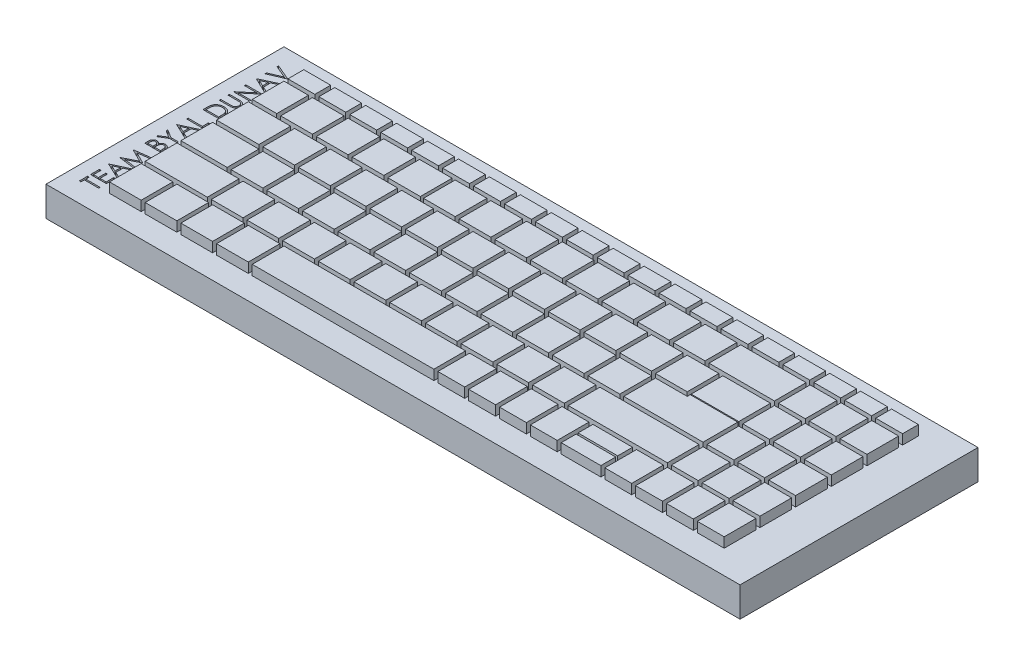
SolidWorks part; units mm, degrees
ref_plane "Front Plane" through (0, 0, 0) normal (0, 0, 1) x (1, 0, 0)
ref_plane "Top Plane" through (0, 0, 0) normal (0, 1, 0) x (1, 0, 0)
ref_plane "Right Plane" through (0, 0, 0) normal (1, 0, 0) x (0, 0, -1)
sketch "Sketch2" plane through (0, 0, 0) normal (0, 1, 0) x (1, 0, 0)
  line L0 (-175, 55) -> (-155, 55) construction
  line L1 (175, -60) -> (-175, -60)
  line L2 (175, -60) -> (175, 60)
  line L3 (175, 60) -> (-175, 60)
  line L4 (-175, -60) -> (-175, 60)
  line L5 (175, -60) -> (0, 0) construction
  line L6 (175, 60) -> (-175, -60) construction
  line L7 (-155, 60) -> (-155, 55) construction
  line L8 (155, 60) -> (155, -60) construction
  line L9 (0, 147.8519) -> (0, -167.8838) construction
  line L10 (-385.2931, 0) -> (301.8933, 0) construction
  line L11 (-175, -55) -> (175, -55) construction
  line L12 (-141.45, 55) -> (175, 55) construction
  line L19 (-160.4167, 55) -> (-175, 60) construction
  line L20 (-155, 47) -> (-155, -60) construction
  point P0 (0, 0)
  point P22 (-148.225, 51)
  dimension "D1" = 350
  dimension "D2" = 120
  dimension "D3" = 10
  dimension "D4" = 310
  dimension "D5" = 20
  dimension "D6" = 20
  dimension "D7" = 10
  dimension "D8" = 13.55
  dimension "D9" = 8
extrude "Boss-Extrude1" add sketch "Sketch2" along normal blind 15
sketch "Sketch3" plane through (0, 15, 0) normal (0, 1, 0) x (1, 0, 0)
  line L0 (-125.85, 50) -> (-125.85, 42)
  line L1 (155, -50) -> (-155, -50)
  line L2 (155, -50) -> (155, 50)
  line L3 (155, 50) -> (-155, 50)
  line L4 (-155, -50) -> (-155, 50)
  line L5 (175, -60) -> (175, 60) construction
  line L6 (-175, 60) -> (-175, -60) construction
  line L7 (-155, 50) -> (-141.45, 50)
  line L8 (-155, 50) -> (-155, 42)
  line L9 (-155, 42) -> (-141.45, 42)
  line L10 (-141.45, 50) -> (-141.45, 42)
  line L11 (175, 60) -> (-175, 60) construction
  line L12 (-141.45, 42) -> (-155, 42)
  line L13 (-141.45, 42) -> (-141.45, 50)
  line L14 (-141.45, 50) -> (-155, 50)
  line L15 (-155, 42) -> (-155, 50)
  line L16 (-141.45, 42) -> (-155, 50) construction
  line L17 (-141.45, 50) -> (-155, 42) construction
  line L18 (-141.45, 42) -> (-155, 42)
  line L19 (-141.45, 42) -> (-141.45, 50)
  line L20 (-141.45, 50) -> (-155, 50)
  line L21 (-155, 42) -> (-155, 50)
  line L22 (-141.45, 42) -> (-155, 50) construction
  line L23 (-141.45, 50) -> (-155, 42) construction
  line L24 (-139.4, 42) -> (-125.85, 42)
  line L25 (-110.25, 50) -> (-110.25, 42)
  line L26 (-123.8, 42) -> (-110.25, 42)
  line L27 (-94.65, 50) -> (-94.65, 42)
  line L28 (-108.2, 42) -> (-94.65, 42)
  line L29 (-79.05, 50) -> (-79.05, 42)
  line L30 (-92.6, 42) -> (-79.05, 42)
  line L31 (-63.45, 50) -> (-63.45, 42)
  line L32 (-77, 42) -> (-63.45, 42)
  line L33 (-47.85, 50) -> (-47.85, 42)
  line L34 (-61.4, 42) -> (-47.85, 42)
  line L35 (-32.25, 50) -> (-32.25, 42)
  line L36 (-45.8, 42) -> (-32.25, 42)
  line L37 (-16.65, 50) -> (-16.65, 42)
  line L38 (-30.2, 42) -> (-16.65, 42)
  line L39 (-1.05, 50) -> (-1.05, 42)
  line L40 (-14.6, 42) -> (-1.05, 42)
  line L41 (14.55, 50) -> (14.55, 42)
  line L42 (1, 42) -> (14.55, 42)
  line L43 (30.15, 50) -> (30.15, 42)
  line L44 (16.6, 42) -> (30.15, 42)
  line L45 (45.75, 50) -> (45.75, 42)
  line L46 (32.2, 42) -> (45.75, 42)
  line L47 (61.35, 50) -> (61.35, 42)
  line L48 (47.8, 42) -> (61.35, 42)
  line L49 (76.95, 50) -> (76.95, 42)
  line L50 (63.4, 42) -> (76.95, 42)
  line L51 (92.55, 50) -> (92.55, 42)
  line L52 (79, 42) -> (92.55, 42)
  line L53 (108.15, 50) -> (108.15, 42)
  line L54 (94.6, 42) -> (108.15, 42)
  line L55 (123.75, 50) -> (123.75, 42)
  line L56 (110.2, 42) -> (123.75, 42)
  line L57 (139.35, 50) -> (139.35, 42)
  line L58 (125.8, 42) -> (139.35, 42)
  line L59 (154.95, 50) -> (154.95, 42)
  line L60 (141.4, 42) -> (154.95, 42)
  line L61 (155, 40) -> (-155, 40) construction
  line L62 (-125.85, 42) -> (-139.4, 42)
  line L63 (-125.85, 42) -> (-125.85, 50)
  line L64 (-125.85, 50) -> (-139.4, 50)
  line L65 (-139.4, 42) -> (-139.4, 50)
  line L66 (-125.85, 42) -> (-139.4, 50) construction
  line L67 (-125.85, 50) -> (-139.4, 42) construction
  line L68 (-110.25, 42) -> (-123.8, 42)
  line L69 (-110.25, 42) -> (-110.25, 50)
  line L70 (-110.25, 50) -> (-123.8, 50)
  line L71 (-123.8, 42) -> (-123.8, 50)
  line L72 (-110.25, 42) -> (-123.8, 50) construction
  line L73 (-110.25, 50) -> (-123.8, 42) construction
  line L74 (-94.65, 42) -> (-108.2, 42)
  line L75 (-94.65, 42) -> (-94.65, 50)
  line L76 (-94.65, 50) -> (-108.2, 50)
  line L77 (-108.2, 42) -> (-108.2, 50)
  line L78 (-94.65, 42) -> (-108.2, 50) construction
  line L79 (-94.65, 50) -> (-108.2, 42) construction
  line L80 (-79.05, 42) -> (-92.6, 42)
  line L81 (-79.05, 42) -> (-79.05, 50)
  line L82 (-79.05, 50) -> (-92.6, 50)
  line L83 (-92.6, 42) -> (-92.6, 50)
  line L84 (-79.05, 42) -> (-92.6, 50) construction
  line L85 (-79.05, 50) -> (-92.6, 42) construction
  line L86 (-63.45, 42) -> (-77, 42)
  line L87 (-63.45, 42) -> (-63.45, 50)
  line L88 (-63.45, 50) -> (-77, 50)
  line L89 (-77, 42) -> (-77, 50)
  line L90 (-63.45, 42) -> (-77, 50) construction
  line L91 (-63.45, 50) -> (-77, 42) construction
  line L92 (-47.85, 42) -> (-61.4, 42)
  line L93 (-47.85, 42) -> (-47.85, 50)
  line L94 (-47.85, 50) -> (-61.4, 50)
  line L95 (-61.4, 42) -> (-61.4, 50)
  line L96 (-47.85, 42) -> (-61.4, 50) construction
  line L97 (-47.85, 50) -> (-61.4, 42) construction
  line L98 (-32.25, 42) -> (-45.8, 42)
  line L99 (-32.25, 42) -> (-32.25, 50)
  line L100 (-32.25, 50) -> (-45.8, 50)
  line L101 (-45.8, 42) -> (-45.8, 50)
  line L102 (-32.25, 42) -> (-45.8, 50) construction
  line L103 (-32.25, 50) -> (-45.8, 42) construction
  line L104 (-16.65, 42) -> (-30.2, 42)
  line L105 (-16.65, 42) -> (-16.65, 50)
  line L106 (-16.65, 50) -> (-30.2, 50)
  line L107 (-30.2, 42) -> (-30.2, 50)
  line L108 (-16.65, 42) -> (-30.2, 50) construction
  line L109 (-16.65, 50) -> (-30.2, 42) construction
  line L110 (-1.05, 42) -> (-14.6, 42)
  line L111 (-1.05, 42) -> (-1.05, 50)
  line L112 (-1.05, 50) -> (-14.6, 50)
  line L113 (-14.6, 42) -> (-14.6, 50)
  line L114 (-1.05, 42) -> (-14.6, 50) construction
  line L115 (-1.05, 50) -> (-14.6, 42) construction
  line L116 (14.55, 42) -> (1, 42)
  line L117 (14.55, 42) -> (14.55, 50)
  line L118 (14.55, 50) -> (1, 50)
  line L119 (1, 42) -> (1, 50)
  line L120 (14.55, 42) -> (1, 50) construction
  line L121 (14.55, 50) -> (1, 42) construction
  line L122 (30.15, 42) -> (16.6, 42)
  line L123 (30.15, 42) -> (30.15, 50)
  line L124 (30.15, 50) -> (16.6, 50)
  line L125 (16.6, 42) -> (16.6, 50)
  line L126 (30.15, 42) -> (16.6, 50) construction
  line L127 (30.15, 50) -> (16.6, 42) construction
  line L128 (45.75, 42) -> (32.2, 42)
  line L129 (45.75, 42) -> (45.75, 50)
  line L130 (45.75, 50) -> (32.2, 50)
  line L131 (32.2, 42) -> (32.2, 50)
  line L132 (45.75, 42) -> (32.2, 50) construction
  line L133 (45.75, 50) -> (32.2, 42) construction
  line L134 (61.35, 42) -> (47.8, 42)
  line L135 (61.35, 42) -> (61.35, 50)
  line L136 (61.35, 50) -> (47.8, 50)
  line L137 (47.8, 42) -> (47.8, 50)
  line L138 (61.35, 42) -> (47.8, 50) construction
  line L139 (61.35, 50) -> (47.8, 42) construction
  line L140 (76.95, 42) -> (63.4, 42)
  line L141 (76.95, 42) -> (76.95, 50)
  line L142 (76.95, 50) -> (63.4, 50)
  line L143 (63.4, 42) -> (63.4, 50)
  line L144 (76.95, 42) -> (63.4, 50) construction
  line L145 (76.95, 50) -> (63.4, 42) construction
  line L146 (92.55, 42) -> (79, 42)
  line L147 (92.55, 42) -> (92.55, 50)
  line L148 (92.55, 50) -> (79, 50)
  line L149 (79, 42) -> (79, 50)
  line L150 (92.55, 42) -> (79, 50) construction
  line L151 (92.55, 50) -> (79, 42) construction
  line L152 (108.15, 42) -> (94.6, 42)
  line L153 (108.15, 42) -> (108.15, 50)
  line L154 (108.15, 50) -> (94.6, 50)
  line L155 (94.6, 42) -> (94.6, 50)
  line L156 (108.15, 42) -> (94.6, 50) construction
  line L157 (108.15, 50) -> (94.6, 42) construction
  line L158 (123.75, 42) -> (110.2, 42)
  line L159 (123.75, 42) -> (123.75, 50)
  line L160 (123.75, 50) -> (110.2, 50)
  line L161 (110.2, 42) -> (110.2, 50)
  line L162 (123.75, 42) -> (110.2, 50) construction
  line L163 (123.75, 50) -> (110.2, 42) construction
  line L164 (139.35, 42) -> (125.8, 42)
  line L165 (139.35, 42) -> (139.35, 50)
  line L166 (139.35, 50) -> (125.8, 50)
  line L167 (125.8, 42) -> (125.8, 50)
  line L168 (139.35, 42) -> (125.8, 50) construction
  line L169 (139.35, 50) -> (125.8, 42) construction
  line L170 (154.95, 42) -> (141.4, 42)
  line L171 (154.95, 42) -> (154.95, 50)
  line L172 (154.95, 50) -> (141.4, 50)
  line L173 (141.4, 42) -> (141.4, 50)
  line L174 (154.95, 42) -> (141.4, 50) construction
  line L175 (154.95, 50) -> (141.4, 42) construction
  line L176 (55.35, 24) -> (39.35, 24)
  line L177 (155, 40) -> (141.45, 40)
  line L178 (155, 40) -> (155, 24)
  line L179 (155, 24) -> (141.45, 24)
  line L180 (141.45, 40) -> (141.45, 24)
  line L181 (155, 40) -> (141.45, 24) construction
  line L182 (155, 24) -> (141.45, 40) construction
  line L183 (139.45, 40) -> (125.9, 40)
  line L184 (139.45, 40) -> (139.45, 24)
  line L185 (139.45, 24) -> (125.9, 24)
  line L186 (125.9, 40) -> (125.9, 24)
  line L187 (139.45, 40) -> (125.9, 24) construction
  line L188 (139.45, 24) -> (125.9, 40) construction
  line L189 (123.9, 40) -> (110.35, 40)
  line L191 (123.9, 24) -> (110.35, 24)
  line L192 (110.35, 40) -> (110.35, 24)
  line L193 (123.9, 40) -> (110.35, 24) construction
  line L194 (123.9, 24) -> (110.35, 40) construction
  line L195 (108.35, 40) -> (75.35, 40)
  line L196 (108.35, 40) -> (108.35, 24)
  line L197 (108.35, 24) -> (75.35, 24)
  line L198 (75.35, 40) -> (75.35, 24)
  line L199 (108.35, 40) -> (75.35, 24) construction
  line L200 (108.35, 24) -> (75.35, 40) construction
  line L201 (73.35, 40) -> (57.35, 40)
  line L202 (73.35, 40) -> (73.35, 24)
  line L203 (73.35, 24) -> (57.35, 24)
  line L204 (57.35, 40) -> (57.35, 24)
  line L205 (73.35, 40) -> (57.35, 24) construction
  line L206 (73.35, 24) -> (57.35, 40) construction
  line L207 (39.35, 40) -> (39.35, 24)
  line L208 (37.35, 24) -> (21.35, 24)
  line L209 (21.35, 40) -> (21.35, 24)
  line L210 (19.35, 24) -> (3.35, 24)
  line L211 (3.35, 40) -> (3.35, 24)
  line L212 (1.35, 24) -> (-14.65, 24)
  line L213 (-14.65, 40) -> (-14.65, 24)
  line L214 (-16.65, 24) -> (-32.65, 24)
  line L215 (-32.65, 40) -> (-32.65, 24)
  line L216 (-34.65, 24) -> (-50.65, 24)
  line L217 (-50.65, 40) -> (-50.65, 24)
  line L218 (-52.65, 24) -> (-68.65, 24)
  line L219 (-68.65, 40) -> (-68.65, 24)
  line L220 (-70.65, 24) -> (-86.65, 24)
  line L221 (-86.65, 40) -> (-86.65, 24)
  line L222 (-88.65, 24) -> (-104.65, 24)
  line L223 (-104.65, 40) -> (-104.65, 24)
  line L224 (-106.65, 24) -> (-122.65, 24)
  line L225 (-122.65, 40) -> (-122.65, 24)
  line L226 (-124.65, 24) -> (-140.65, 24)
  line L227 (-140.65, 40) -> (-140.65, 24)
  line L228 (55.35, 24) -> (55.35, 40)
  line L229 (55.35, 40) -> (39.35, 40)
  line L230 (123.9, 40) -> (123.9, 24)
  line L231 (21.35, 24) -> (37.35, 24)
  line L232 (21.35, 24) -> (21.35, 40)
  line L233 (21.35, 40) -> (37.35, 40)
  line L234 (37.35, 24) -> (37.35, 40)
  line L235 (21.35, 24) -> (37.35, 40) construction
  line L236 (21.35, 40) -> (37.35, 24) construction
  line L237 (3.35, 24) -> (19.35, 24)
  line L238 (3.35, 24) -> (3.35, 40)
  line L239 (3.35, 40) -> (19.35, 40)
  line L240 (19.35, 24) -> (19.35, 40)
  line L241 (3.35, 24) -> (19.35, 40) construction
  line L242 (3.35, 40) -> (19.35, 24) construction
  line L243 (-14.65, 24) -> (1.35, 24)
  line L244 (-14.65, 24) -> (-14.65, 40)
  line L245 (-14.65, 40) -> (1.35, 40)
  line L246 (1.35, 24) -> (1.35, 40)
  line L247 (-14.65, 24) -> (1.35, 40) construction
  line L248 (-14.65, 40) -> (1.35, 24) construction
  line L249 (-32.65, 24) -> (-16.65, 24)
  line L250 (-32.65, 24) -> (-32.65, 40)
  line L251 (-32.65, 40) -> (-16.65, 40)
  line L252 (-16.65, 24) -> (-16.65, 40)
  line L253 (-32.65, 24) -> (-16.65, 40) construction
  line L254 (-32.65, 40) -> (-16.65, 24) construction
  line L255 (-50.65, 24) -> (-34.65, 24)
  line L256 (-50.65, 24) -> (-50.65, 40)
  line L257 (-50.65, 40) -> (-34.65, 40)
  line L258 (-34.65, 24) -> (-34.65, 40)
  line L259 (-50.65, 24) -> (-34.65, 40) construction
  line L260 (-50.65, 40) -> (-34.65, 24) construction
  line L261 (-68.65, 24) -> (-52.65, 24)
  line L262 (-68.65, 24) -> (-68.65, 40)
  line L263 (-68.65, 40) -> (-52.65, 40)
  line L264 (-52.65, 24) -> (-52.65, 40)
  line L265 (-68.65, 24) -> (-52.65, 40) construction
  line L266 (-68.65, 40) -> (-52.65, 24) construction
  line L267 (-86.65, 24) -> (-70.225, 24)
  line L268 (-86.65, 24) -> (-86.65, 40)
  line L269 (-86.65, 40) -> (-70.225, 40)
  line L270 (-70.225, 24) -> (-70.225, 40)
  line L271 (-86.65, 24) -> (-70.225, 40) construction
  line L272 (-86.65, 40) -> (-70.225, 24) construction
  line L273 (-104.65, 24) -> (-88.65, 24)
  line L274 (-104.65, 24) -> (-104.65, 40)
  line L275 (-104.65, 40) -> (-88.65, 40)
  line L276 (-88.65, 24) -> (-88.65, 40)
  line L277 (-104.65, 24) -> (-88.65, 40) construction
  line L278 (-104.65, 40) -> (-88.65, 24) construction
  line L279 (-122.65, 24) -> (-106.65, 24)
  line L280 (-122.65, 24) -> (-122.65, 40)
  line L281 (-122.65, 40) -> (-106.65, 40)
  line L282 (-106.65, 24) -> (-106.65, 40)
  line L283 (-122.65, 24) -> (-106.65, 40) construction
  line L284 (-122.65, 40) -> (-106.65, 24) construction
  line L285 (-140.65, 24) -> (-124.65, 24)
  line L286 (-140.65, 24) -> (-140.65, 40)
  line L287 (-140.65, 40) -> (-124.65, 40)
  line L288 (-124.65, 24) -> (-124.65, 40)
  line L289 (-140.65, 24) -> (-124.65, 40) construction
  line L290 (-140.65, 40) -> (-124.65, 24) construction
  line L291 (-155, 40) -> (-142.65, 40)
  line L292 (-155, 40) -> (-155, 24)
  line L293 (-155, 24) -> (-142.65, 24)
  line L294 (-142.65, 40) -> (-142.65, 24)
  line L295 (-155, 40) -> (-142.65, 24) construction
  line L296 (-155, 24) -> (-142.65, 40) construction
  line L297 (110.35, 22) -> (110.35, 6)
  line L298 (123.9, 22) -> (123.9, 6)
  line L299 (123.9, 6) -> (110.35, 6)
  line L300 (125.9, 22) -> (125.9, 6)
  line L301 (139.45, 6) -> (125.9, 6)
  line L302 (139.45, 22) -> (139.45, 6)
  line L303 (141.45, 22) -> (141.45, 6)
  line L304 (155, 6) -> (141.45, 6)
  line L305 (110.35, 4) -> (110.35, -12)
  line L306 (123.9, 4) -> (123.9, -12)
  line L307 (123.9, -12) -> (110.35, -12)
  line L308 (125.9, 4) -> (125.9, -12)
  line L309 (139.45, -12) -> (125.9, -12)
  line L310 (139.45, 4) -> (139.45, -12)
  line L311 (141.45, 4) -> (141.45, -12)
  line L312 (155, -12) -> (141.45, -12)
  line L313 (110.35, -14) -> (110.35, -30)
  line L314 (123.9, -14) -> (123.9, -30)
  line L315 (123.9, -30) -> (110.35, -30)
  line L316 (125.9, -14) -> (125.9, -30)
  line L317 (139.45, -30) -> (125.9, -30)
  line L318 (139.45, -14) -> (139.45, -30)
  line L319 (141.45, -14) -> (141.45, -30)
  line L320 (155, -30) -> (141.45, -30)
  line L321 (110.35, -32) -> (110.35, -48)
  line L322 (123.9, -32) -> (123.9, -48)
  line L323 (123.9, -48) -> (110.35, -48)
  line L324 (125.9, -32) -> (125.9, -48)
  line L325 (139.45, -48) -> (125.9, -48)
  line L326 (139.45, -32) -> (139.45, -48)
  line L327 (141.45, -32) -> (141.45, -48)
  line L328 (155, -48) -> (141.45, -48)
  line L329 (110.35, 22) -> (123.9, 22)
  line L330 (125.9, 22) -> (139.45, 22)
  line L331 (141.45, 22) -> (155, 22)
  line L332 (110.35, 4) -> (123.9, 4)
  line L333 (125.9, 4) -> (139.45, 4)
  line L334 (141.45, 4) -> (155, 4)
  line L335 (110.35, -14) -> (123.9, -14)
  line L336 (125.9, -14) -> (139.45, -14)
  line L337 (141.45, -14) -> (155, -14)
  line L338 (110.35, -32) -> (123.9, -32)
  line L339 (125.9, -32) -> (139.45, -32)
  line L340 (141.45, -32) -> (155, -32)
  line L341 (155, 22) -> (-155, 22) construction
  line L342 (155, 6) -> (-155, 6) construction
  line L343 (48.35, 22) -> (48.35, 6)
  line L344 (108.35, 22) -> (84.35, 22)
  line L345 (108.35, 22) -> (108.35, 6)
  line L346 (108.35, 6) -> (84.35, 6)
  line L347 (84.35, 22) -> (84.35, 6)
  line L348 (108.35, 22) -> (84.35, 6) construction
  line L349 (108.35, 6) -> (84.35, 22) construction
  line L350 (82.35, 22) -> (66.35, 22)
  line L351 (82.35, 22) -> (82.35, 6)
  line L352 (82.35, 6) -> (66.35, 6)
  line L353 (66.35, 22) -> (66.35, 6)
  line L354 (82.35, 22) -> (66.35, 6) construction
  line L355 (82.35, 6) -> (66.35, 22) construction
  line L356 (64.35, 6) -> (48.35, 6)
  line L357 (30.35, 22) -> (30.35, 6)
  line L358 (46.35, 6) -> (30.35, 6)
  line L359 (12.35, 22) -> (12.35, 6)
  line L360 (28.35, 6) -> (12.35, 6)
  line L361 (-5.65, 22) -> (-5.65, 6)
  line L362 (10.35, 6) -> (-5.65, 6)
  line L363 (-23.65, 22) -> (-23.65, 6)
  line L364 (-7.65, 6) -> (-23.65, 6)
  line L365 (-41.65, 22) -> (-41.65, 6)
  line L366 (-25.65, 6) -> (-41.65, 6)
  line L367 (-59.65, 22) -> (-59.65, 6)
  line L368 (-43.65, 6) -> (-59.65, 6)
  line L369 (-77.65, 22) -> (-77.65, 6)
  line L370 (-61.65, 6) -> (-77.65, 6)
  line L371 (-95.65, 22) -> (-95.65, 6)
  line L372 (-79.65, 6) -> (-95.65, 6)
  line L373 (-113.65, 22) -> (-113.65, 6)
  line L374 (-97.65, 6) -> (-113.65, 6)
  line L375 (-131.65, 22) -> (-131.65, 6)
  line L376 (-115.65, 6) -> (-131.65, 6)
  line L377 (28.35, 6) -> (28.35, 22)
  line L378 (-131.65, 6) -> (-115.65, 6)
  line L379 (-131.65, 6) -> (-131.65, 22)
  line L380 (-131.65, 22) -> (-115.65, 22)
  line L381 (-115.65, 6) -> (-115.65, 22)
  line L382 (-131.65, 6) -> (-115.65, 22) construction
  line L383 (-131.65, 22) -> (-115.65, 6) construction
  line L384 (-113.65, 6) -> (-97.65, 6)
  line L385 (-113.65, 6) -> (-113.65, 22)
  line L386 (-113.65, 22) -> (-97.65, 22)
  line L387 (-97.65, 6) -> (-97.65, 22)
  line L388 (-113.65, 6) -> (-97.65, 22) construction
  line L389 (-113.65, 22) -> (-97.65, 6) construction
  line L390 (-95.65, 6) -> (-79.65, 6)
  line L391 (-95.65, 6) -> (-95.65, 22)
  line L392 (-95.65, 22) -> (-79.65, 22)
  line L393 (-79.65, 6) -> (-79.65, 22)
  line L394 (-95.65, 6) -> (-79.65, 22) construction
  line L395 (-95.65, 22) -> (-79.65, 6) construction
  line L396 (-77.65, 6) -> (-61.65, 6)
  line L397 (-77.65, 6) -> (-77.65, 22)
  line L398 (-77.65, 22) -> (-61.65, 22)
  line L399 (-61.65, 6) -> (-61.65, 22)
  line L400 (-77.65, 6) -> (-61.65, 22) construction
  line L401 (-77.65, 22) -> (-61.65, 6) construction
  line L402 (-59.65, 6) -> (-43.65, 6)
  line L403 (-59.65, 6) -> (-59.65, 22)
  line L404 (-59.65, 22) -> (-43.65, 22)
  line L405 (-43.65, 6) -> (-43.65, 22)
  line L406 (-59.65, 6) -> (-43.65, 22) construction
  line L407 (-59.65, 22) -> (-43.65, 6) construction
  line L408 (-41.65, 6) -> (-25.65, 6)
  line L409 (-41.65, 6) -> (-41.65, 22)
  line L410 (-41.65, 22) -> (-25.65, 22)
  line L411 (-25.65, 6) -> (-25.65, 22)
  line L412 (-41.65, 6) -> (-25.65, 22) construction
  line L413 (-41.65, 22) -> (-25.65, 6) construction
  line L414 (-23.65, 6) -> (-7.65, 6)
  line L415 (-23.65, 6) -> (-23.65, 22)
  line L416 (-23.65, 22) -> (-7.65, 22)
  line L417 (-7.65, 6) -> (-7.65, 22)
  line L418 (-23.65, 6) -> (-7.65, 22) construction
  line L419 (-23.65, 22) -> (-7.65, 6) construction
  line L420 (10.35, 6) -> (-5.65, 6)
  line L421 (10.35, 6) -> (10.35, 22)
  line L422 (10.35, 22) -> (-5.65, 22)
  line L423 (-5.65, 6) -> (-5.65, 22)
  line L424 (10.35, 6) -> (-5.65, 22) construction
  line L425 (10.35, 22) -> (-5.65, 6) construction
  line L426 (28.35, 22) -> (12.35, 22)
  line L427 (46.35, 6) -> (46.35, 22)
  line L428 (46.35, 22) -> (30.35, 22)
  line L429 (64.35, 6) -> (64.35, 22)
  line L430 (64.35, 22) -> (48.35, 22)
  line L432 (-155, 6) -> (-133.65, 6)
  line L433 (-155, 6) -> (-155, 22)
  line L434 (-155, 22) -> (-133.65, 22)
  line L435 (-133.65, 6) -> (-133.65, 22)
  line L436 (-155, 6) -> (-133.65, 22) construction
  line L437 (-155, 22) -> (-133.65, 6) construction
  point P0 (0, 0)
  point P9 (-148.225, 47.8145)
  point P17 (-148.225, 46)
  point P18 (-148.225, 46)
  point P20 (-132.625, 46)
  point P78 (-117.025, 46)
  point P80 (-101.425, 46)
  point P82 (-85.825, 46)
  point P84 (-70.225, 46)
  point P86 (-54.625, 46)
  point P88 (-39.025, 46)
  point P90 (-23.425, 46)
  point P92 (-7.825, 46)
  point P94 (7.775, 46)
  point P96 (23.375, 46)
  point P98 (38.975, 46)
  point P100 (54.575, 46)
  point P102 (70.175, 46)
  point P104 (85.775, 46)
  point P106 (101.375, 46)
  point P108 (116.975, 46)
  point P110 (132.575, 46)
  point P112 (148.175, 46)
  point P118 (148.225, 32)
  point P123 (132.675, 32)
  point P128 (117.125, 32)
  point P133 (91.85, 32)
  point P134 (125.9, 32)
  point P139 (65.35, 32)
  point P175 (29.35, 32)
  point P177 (11.35, 32)
  point P179 (-6.65, 32)
  point P181 (-24.65, 32)
  point P183 (-42.65, 32)
  point P185 (-60.65, 32)
  point P188 (-78.4375, 32)
  point P190 (-96.65, 32)
  point P192 (-114.65, 32)
  point P194 (-132.65, 32)
  point P198 (-148.825, 32)
  point P199 (-142.65, 32)
  point P200 (21.35, 32)
  point P250 (117.125, 22)
  point P256 (96.35, 14)
  point P261 (74.35, 14)
  point P262 (82.35, 14)
  point P264 (-123.65, 14)
  point P299 (-105.65, 14)
  point P301 (-87.65, 14)
  point P303 (-69.65, 14)
  point P305 (-51.65, 14)
  point P307 (-33.65, 14)
  point P309 (-15.65, 14)
  point P312 (2.35, 14)
  point P318 (-144.325, 14)
  dimension "D1" = 310
  dimension "D2" = 100
  dimension "D3" = 13.55
  dimension "D4" = 8
  dimension "D5" = 20
  dimension "D6" = 20
  dimension "D7" = 10
  dimension "D8" = 20
  dimension "D9" = 2
  dimension "D10" = 16
  dimension "D11" = 13.55
  dimension "D12" = 2
  dimension "D13" = 13.55
  dimension "D14" = 16
  dimension "D15" = 16
  dimension "D16" = 16
  dimension "D17" = 16
  dimension "D18" = 33
  dimension "D19" = 2
  dimension "D20" = 5
  dimension "D21" = 2
  dimension "D22" = 16
  dimension "D23" = 12
  dimension "D24" = 2
  dimension "D25" = 2
  dimension "D26" = 2
  dimension "D27" = 2
  dimension "D28" = 12.35
  dimension "D29" = 2
  dimension "D30" = 16
  dimension "D31" = 2
  dimension "D32" = 24
  dimension "D33" = 2
  dimension "D34" = 16
  dimension "D35" = 2
  dimension "D36" = 12
  dimension "D37" = 2
  dimension "D38" = 2
extrude "Boss-Extrude2" add sketch "Sketch3" along normal blind 5 contours L10 L3 L4 L9 | L432 L435 L434 L4 | L226 L288 L287 L227 | L294 L291 L4 L293 | L65 L24 L0 L3 | L376 L381 L380 L375 | L374 L387 L386 L373 | L83 L30 L29 L3 | L267 L270 L269 L221 L220 | L372 L393 L392 L371 | L370 L399 L398 L369 | L222 L276 L275 L223 | L224 L282 L281 L225 | L71 L26 L25 L3 | L77 L28 L27 L3 | L89 L32 L31 L3 | L218 L264 L263 L219 | L95 L34 L33 L3 | L368 L405 L404 L367 | L216 L258 L257 L217 | L101 L36 L35 L3 | L214 L252 L251 L215 | L366 L411 L410 L365 | L364 L417 L416 L363 | L212 L246 L245 L213 | L107 L38 L37 L3 | L113 L40 L39 L3 | L119 L42 L41 L3 | L210 L240 L239 L211 | L421 L422 L361 L362 | L377 L426 L359 L360 | L125 L44 L43 L3 | L228 L229 L207 L176 | L208 L234 L233 L209 | L131 L46 L45 L3 | L427 L428 L357 L358 | L429 L430 L343 L356 | L201 L204 L203 L202 | L143 L50 L49 L3 | L137 L48 L47 L3 | L149 L52 L51 L3 | L350 L353 L352 L351 | L195 L198 L197 L196 | L344 L347 L346 L345 | L329 L297 L299 L298 | L230 L189 L192 L191 | L183 L186 L185 L184 | L331 L303 L304 L2 | L330 L300 L301 L302 | L332 L305 L307 L306 | L333 L308 L309 L310 | L334 L311 L312 L2 | L337 L319 L320 L2 | L335 L313 L315 L314 | L338 L321 L323 L322 | L340 L327 L328 L2 | L336 L316 L317 L318 | L339 L324 L325 L326 | L155 L54 L53 L3 | L173 L60 L59 L3 | L177 L180 L179 L2 | L161 L56 L55 L3 | L167 L58 L57 L3 region at (-132.625, 15, -46) region at (-117.025, 15, -46) region at (-148.225, 15, -46) region at (-101.425, 15, -46) region at (-85.825, 15, -46) region at (-148.825, 15, -32) region at (-70.225, 15, -46) region at (-144.325, 15, -14) region at (-54.625, 15, -46) region at (-39.025, 15, -46) region at (148.225, 15, 40) region at (-23.425, 15, -46) region at (148.225, 15, 22) region at (-7.825, 15, -46) region at (148.225, 15, 4) region at (7.775, 15, -46) region at (148.225, 15, -14) region at (23.375, 15, -46) region at (148.225, 15, -32) region at (38.975, 15, -46) region at (148.175, 15, -46) region at (54.575, 15, -46) region at (132.575, 15, -46) region at (70.175, 15, -46) region at (116.975, 15, -46) region at (85.775, 15, -46) region at (101.375, 15, -46) region at (47.35, 15, -32) region at (132.675, 15, -32) region at (117.125, 15, -32) region at (91.85, 15, -32) region at (65.35, 15, -32) region at (29.35, 15, -32) region at (11.35, 15, -32) region at (-6.65, 15, -32) region at (-24.65, 15, -32) region at (-42.65, 15, -32) region at (-60.65, 15, -32) region at (-78.4375, 15, -32) region at (-96.65, 15, -32) region at (-114.65, 15, -32) region at (-132.65, 15, -32) region at (117.125, 15, -14) region at (132.675, 15, -14) region at (117.125, 15, 4) region at (132.675, 15, 4) region at (117.125, 15, 22) region at (132.675, 15, 22) region at (117.125, 15, 40) region at (132.675, 15, 40) region at (56.35, 15, -14) region at (96.35, 15, -14) region at (74.35, 15, -14) region at (38.35, 15, -14) region at (20.35, 15, -14) region at (2.35, 15, -14) region at (-15.65, 15, -14) region at (-33.65, 15, -14) region at (-51.65, 15, -14) region at (-69.65, 15, -14)
sketch "Sketch4" plane through (0, 15, 0) normal (0, 1, 0) x (1, 0, 0)
  line L0 (155, -12) -> (-175, -12) construction
  line L1 (-175, 60) -> (-175, -60) construction
  line L2 (155, 4) -> (108.35, 4) construction
  line L3 (110.35, 4) -> (110.35, -12) construction
  line L4 (84.35, 4) -> (68.35, 4)
  line L5 (108.35, 4) -> (108.35, -12)
  line L6 (108.35, -12) -> (68.35, -12)
  line L7 (68.35, 4) -> (68.35, -12)
  line L8 (108.35, 4) -> (68.35, -12) construction
  line L9 (108.35, -12) -> (68.35, 4) construction
  line L11 (84.35, 5.4992) -> (84.35, 4)
  line L14 (84.35, 4) -> (-175, 4) construction
  line L15 (108.35, 4) -> (108.35, 5.4992)
  line L16 (108.35, 5.4992) -> (84.35, 5.4992)
  line L17 (32.35, 4) -> (32.35, -12)
  line L18 (66.35, 4) -> (50.35, 4)
  line L19 (66.35, 4) -> (66.35, -12)
  line L20 (66.35, -12) -> (50.35, -12)
  line L21 (50.35, 4) -> (50.35, -12)
  line L22 (66.35, 4) -> (50.35, -12) construction
  line L23 (66.35, -12) -> (50.35, 4) construction
  line L24 (48.35, -12) -> (32.35, -12)
  line L25 (14.35, 4) -> (14.35, -12)
  line L26 (30.35, -12) -> (14.35, -12)
  line L27 (-3.65, 4) -> (-3.65, -12)
  line L28 (12.35, -12) -> (-3.65, -12)
  line L29 (-21.65, 4) -> (-21.65, -12)
  line L30 (-5.65, -12) -> (-21.65, -12)
  line L31 (-39.65, 4) -> (-39.65, -12)
  line L32 (-23.65, -12) -> (-39.65, -12)
  line L33 (-57.65, 4) -> (-57.65, -12)
  line L34 (-41.65, -12) -> (-57.65, -12)
  line L35 (-75.65, 4) -> (-75.65, -12)
  line L36 (-59.65, -12) -> (-75.65, -12)
  line L37 (-93.65, 4) -> (-93.65, -12)
  line L38 (-77.65, -12) -> (-93.65, -12)
  line L39 (-111.65, 4) -> (-111.65, -12)
  line L40 (-95.65, -12) -> (-111.65, -12)
  line L41 (-129.65, 4) -> (-129.65, -12)
  line L42 (-113.65, -12) -> (-129.65, -12)
  line L43 (48.35, -12) -> (48.35, 4)
  line L44 (48.35, 4) -> (32.35, 4)
  line L45 (30.35, -12) -> (30.35, 4)
  line L46 (30.35, 4) -> (14.35, 4)
  line L47 (12.35, -12) -> (12.35, 4)
  line L48 (12.35, 4) -> (-3.65, 4)
  line L49 (-5.65, -12) -> (-5.65, 4)
  line L50 (-5.65, 4) -> (-21.65, 4)
  line L51 (-23.65, -12) -> (-23.65, 4)
  line L52 (-23.65, 4) -> (-39.65, 4)
  line L53 (-41.65, -12) -> (-41.65, 4)
  line L54 (-41.65, 4) -> (-57.65, 4)
  line L55 (-59.65, -12) -> (-59.65, 4)
  line L56 (-59.65, 4) -> (-75.65, 4)
  line L57 (-77.65, -12) -> (-77.65, 4)
  line L58 (-77.65, 4) -> (-93.65, 4)
  line L59 (-95.65, -12) -> (-95.65, 4)
  line L60 (-95.65, 4) -> (-111.65, 4)
  line L61 (-113.65, -12) -> (-113.65, 4)
  line L62 (-113.65, 4) -> (-129.65, 4)
  line L63 (-155, 6) -> (-155, -18.2543) construction
  line L65 (-155, 4) -> (-131.65, 4)
  line L66 (-155, 4) -> (-155, -12)
  line L67 (-155, -12) -> (-131.65, -12)
  line L68 (-131.65, 4) -> (-131.65, -12)
  line L69 (-155, 4) -> (-131.65, -12) construction
  line L70 (-155, -12) -> (-131.65, 4) construction
  point P12 (88.35, -4)
  point P24 (58.35, -4)
  point P70 (-143.325, -4)
  dimension "D1" = 2
  dimension "D2" = 40
  dimension "D3" = 2
  dimension "D4" = 16
  dimension "D6" = 2
  dimension "D7" = 2
  dimension "D8" = 2
  dimension "D5" = 11
extrude "Boss-Extrude3" add sketch "Sketch4" along normal blind 5
sketch "Sketch5" plane through (0, 15, 0) normal (0, 1, 0) x (1, 0, 0)
  line L0 (155, -14) -> (-175, -14) construction
  line L1 (-175, 60) -> (-175, -60) construction
  line L2 (155, -30) -> (-175, -30) construction
  line L3 (110.35, -14) -> (110.35, -30) construction
  line L4 (108.35, -14) -> (58.35, -14)
  line L5 (108.35, -14) -> (108.35, -30)
  line L6 (108.35, -30) -> (58.35, -30)
  line L7 (58.35, -14) -> (58.35, -30)
  line L8 (108.35, -14) -> (58.35, -30) construction
  line L9 (108.35, -30) -> (58.35, -14) construction
  line L10 (22.35, -14) -> (22.35, -30)
  line L11 (56.35, -14) -> (40.35, -14)
  line L12 (56.35, -14) -> (56.35, -30)
  line L13 (56.35, -30) -> (40.35, -30)
  line L14 (40.35, -14) -> (40.35, -30)
  line L15 (56.35, -14) -> (40.35, -30) construction
  line L16 (56.35, -30) -> (40.35, -14) construction
  line L17 (38.35, -30) -> (22.35, -30)
  line L18 (4.35, -14) -> (4.35, -30)
  line L19 (20.35, -30) -> (4.35, -30)
  line L20 (-13.65, -14) -> (-13.65, -30)
  line L21 (2.35, -30) -> (-13.65, -30)
  line L22 (-31.65, -14) -> (-31.65, -30)
  line L23 (-15.65, -30) -> (-31.65, -30)
  line L24 (-49.65, -14) -> (-49.65, -30)
  line L25 (-33.65, -30) -> (-49.65, -30)
  line L26 (-67.65, -14) -> (-67.65, -30)
  line L27 (-51.65, -30) -> (-67.65, -30)
  line L28 (-85.65, -14) -> (-85.65, -30)
  line L29 (-69.65, -30) -> (-85.65, -30)
  line L30 (-103.65, -14) -> (-103.65, -30)
  line L31 (-87.65, -30) -> (-103.65, -30)
  line L32 (-121.65, -14) -> (-121.65, -30)
  line L33 (-105.65, -30) -> (-121.65, -30)
  line L34 (-105.65, -30) -> (-105.65, -14)
  line L35 (-105.65, -14) -> (-121.65, -14)
  line L36 (-87.65, -30) -> (-87.65, -14)
  line L37 (-87.65, -14) -> (-103.65, -14)
  line L38 (-69.65, -30) -> (-69.65, -14)
  line L39 (-69.65, -14) -> (-85.65, -14)
  line L40 (-51.65, -30) -> (-51.65, -14)
  line L41 (-51.65, -14) -> (-67.65, -14)
  line L42 (-33.65, -30) -> (-33.65, -14)
  line L43 (-33.65, -14) -> (-49.65, -14)
  line L44 (-15.65, -30) -> (-15.65, -14)
  line L45 (-15.65, -14) -> (-32.2067, -14)
  line L46 (2.35, -30) -> (2.35, -14)
  line L47 (2.35, -14) -> (-13.65, -14)
  line L48 (20.35, -30) -> (20.35, -14)
  line L49 (20.35, -14) -> (4.35, -14)
  line L50 (38.35, -30) -> (38.35, -14)
  line L51 (22.35, -14) -> (38.35, -14)
  line L52 (-155, -12) -> (-155, -64.2807) construction
  line L54 (-155, -14) -> (-123.65, -14)
  line L55 (-155, -14) -> (-155, -30)
  line L56 (-155, -30) -> (-123.65, -30)
  line L57 (-123.65, -14) -> (-123.65, -30)
  line L58 (-155, -14) -> (-123.65, -30) construction
  line L59 (-155, -30) -> (-123.65, -14) construction
  point P13 (83.35, -22)
  point P20 (48.35, -22)
  point P64 (-139.325, -22)
  dimension "D1" = 50
  dimension "D2" = 2
  dimension "D3" = 16
  dimension "D4" = 2
  dimension "D5" = 10
  dimension "D6" = 2
  dimension "D7" = 2
  dimension "D8" = 2
extrude "Boss-Extrude4" add sketch "Sketch5" along normal blind 5 contours L57 L54 L55 L56 | L34 L35 L32 L33 | L36 L37 L30 L31 | L38 L39 L28 L29 | L40 L41 L26 L27 | L44 L45 L22 L23 | L48 L49 L18 L19 | L11 L14 L13 L12 | L4 L7 L6 L5 | L42 L43 L24 L25 | L46 L47 L20 L21 | L10 L17 L50 L51 region at (83.35, 15, 22) region at (48.35, 15, 22) region at (12.35, 15, 22) region at (-23.65, 15, 22) region at (-59.65, 15, 22) region at (-77.65, 15, 22) region at (-95.65, 15, 22) region at (-113.65, 15, 22) region at (-139.325, 15, 22)
sketch "Sketch8" plane through (0, 15, 0) normal (0, 1, 0) x (1, 0, 0)
  line L0 (155, -32) -> (-175, -32) construction
  line L1 (-175, 60) -> (-175, -60) construction
  line L2 (155, -48) -> (-175, -48) construction
  line L3 (110.35, -32) -> (110.35, -48) construction
  line L4 (108.35, -32) -> (94.8, -32)
  line L5 (108.35, -32) -> (108.35, -48)
  line L6 (108.35, -48) -> (94.8, -48)
  line L7 (94.8, -32) -> (94.8, -48)
  line L8 (108.35, -32) -> (94.8, -48) construction
  line L9 (108.35, -48) -> (94.8, -32) construction
  line L10 (41.7, -32) -> (41.7, -48)
  line L11 (92.8, -32) -> (72.8, -32)
  line L12 (92.8, -32) -> (92.8, -39.5)
  line L13 (92.8, -48) -> (72.8, -48)
  line L14 (72.8, -32) -> (72.8, -39.5)
  line L15 (92.8, -32) -> (72.8, -48) construction
  line L16 (92.8, -48) -> (72.8, -32) construction
  line L17 (70.8, -32) -> (57.25, -32)
  line L18 (70.8, -32) -> (70.8, -48)
  line L19 (70.8, -48) -> (57.25, -48)
  line L20 (57.25, -32) -> (57.25, -48)
  line L21 (70.8, -32) -> (57.25, -48) construction
  line L22 (70.8, -48) -> (57.25, -32) construction
  line L23 (55.25, -48) -> (41.7, -48)
  line L24 (26.15, -32) -> (26.15, -48)
  line L25 (39.7, -48) -> (26.15, -48)
  line L26 (10.6, -32) -> (10.6, -48)
  line L27 (24.15, -48) -> (10.6, -48)
  line L28 (55.25, -48) -> (55.25, -32)
  line L29 (55.25, -32) -> (41.7, -32)
  line L30 (39.7, -48) -> (39.7, -32)
  line L31 (39.7, -32) -> (26.15, -32)
  line L32 (24.15, -48) -> (24.15, -32)
  line L33 (24.15, -32) -> (10.6, -32)
  line L34 (-155, -30) -> (-155, -58.0445) construction
  line L35 (8.6, -32) -> (-83, -32)
  line L36 (8.6, -32) -> (8.6, -48)
  line L37 (8.6, -48) -> (-83, -48)
  line L38 (-83, -32) -> (-83, -48)
  line L39 (8.6, -32) -> (-83, -48) construction
  line L40 (8.6, -48) -> (-83, -32) construction
  line L41 (-121, -32) -> (-121, -48)
  line L42 (-155, -32) -> (-139, -32)
  line L43 (-155, -32) -> (-155, -48)
  line L44 (-155, -48) -> (-139, -48)
  line L45 (-139, -32) -> (-139, -48)
  line L46 (-155, -32) -> (-139, -48) construction
  line L47 (-155, -48) -> (-139, -32) construction
  line L48 (-137, -48) -> (-121, -48)
  line L49 (-103, -32) -> (-103, -48)
  line L50 (-119, -48) -> (-103, -48)
  line L51 (-85, -32) -> (-85, -48)
  line L52 (-101, -48) -> (-85, -48)
  line L53 (-137, -48) -> (-137, -32)
  line L54 (-137, -32) -> (-121, -32)
  line L55 (-119, -48) -> (-119, -32)
  line L56 (-119, -32) -> (-103, -32)
  line L57 (-101, -48) -> (-101, -32)
  line L58 (-101, -32) -> (-85, -32)
  line L59 (72.8, -40.5) -> (72.8, -48)
  line L60 (72.8, -32) -> (92.8, -32)
  line L61 (72.8, -32) -> (72.8, -39.5)
  line L62 (72.8, -39.5) -> (92.8, -39.5)
  line L63 (92.8, -32) -> (92.8, -39.5)
  line L64 (72.8, -32) -> (92.8, -39.5) construction
  line L65 (72.8, -39.5) -> (92.8, -32) construction
  line L66 (72.8, -48) -> (92.8, -48)
  line L67 (72.8, -48) -> (72.8, -40.5)
  line L68 (72.8, -40.5) -> (92.8, -40.5)
  line L69 (92.8, -48) -> (92.8, -40.5)
  line L70 (72.8, -48) -> (92.8, -40.5) construction
  line L71 (72.8, -40.5) -> (92.8, -48) construction
  line L72 (92.8, -40.5) -> (92.8, -48)
  point P12 (101.575, -40)
  point P19 (82.8, -40)
  point P20 (94.8, -40)
  point P25 (64.025, -40)
  point P42 (-37.2, -40)
  point P43 (55.25, -40)
  point P51 (-147, -40)
  point P66 (82.8, -35.75)
  point P69 (82.8, -44.25)
  dimension "D1" = 13.55
  dimension "D2" = 2
  dimension "D3" = 20
  dimension "D4" = 2
  dimension "D5" = 13.55
  dimension "D6" = 2
  dimension "D8" = 13.55
  dimension "D9" = 2
  dimension "D10" = 2
  dimension "D11" = 2
  dimension "D12" = 16
  dimension "D13" = 4
  dimension "D14" = 2
  dimension "D15" = 91.6
  dimension "D16" = 16
  dimension "D17" = 7.5
  dimension "D18" = 7.5
  dimension "D7" = 4
extrude "Boss-Extrude5" add sketch "Sketch8" along normal blind 5 contours L45 L42 L43 L44 | L54 L53 L48 L41 | L58 L57 L52 L51 | L35 L38 L37 L36 | L32 L33 L26 L27 | L30 L31 L24 L25 | L28 L29 L10 L23 | L17 L20 L19 L18 | L13 L69 L68 L59 | L14 L62 L12 L11 | L4 L7 L6 L5 | L49 L50 L55 L56 region at (101.575, 15, 40) region at (48.475, 15, 40) region at (82.8, 15, 35.75) region at (82.8, 15, 44.25) region at (64.025, 15, 40) region at (32.925, 15, 40) region at (17.375, 15, 40) region at (-37.2, 15, 40) region at (-129, 15, 40) region at (-147, 15, 40) region at (-93, 15, 40)
sketch "Sketch16" plane through (0, 15, 0) normal (0, 1, 0) x (1, 0, 0)
  line L0 (-160, 60) -> (-160, -60) construction
  line L1 (175, 60) -> (-175, 60) construction
  line L2 (-175, -60) -> (175, -60) construction
  line L3 (-175, 60) -> (-175, -60) construction
  text T0 "TEAM BYAL DUNAV" font "Century Gothic" height 8
  dimension "D1" = 15
extrude "Cut-Extrude5" cut sketch "Sketch16" against normal blind 5
